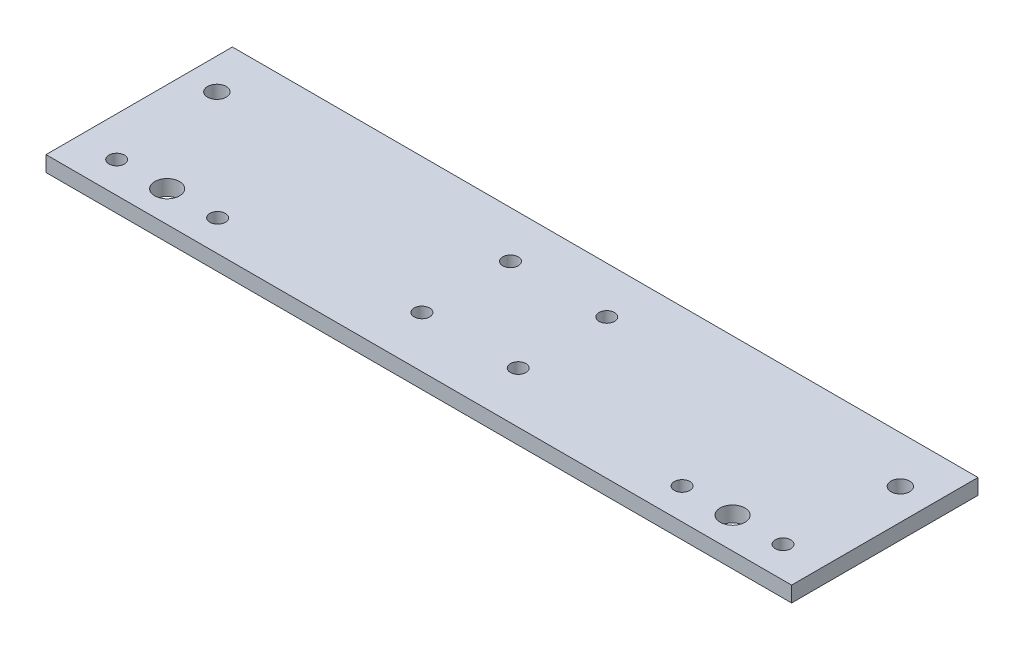
SolidWorks part; units mm, degrees
ref_plane "Front Plane" through (0, 0, 0) normal (0, 0, 1) x (1, 0, 0)
ref_plane "Top Plane" through (0, 0, 0) normal (0, 1, 0) x (1, 0, 0)
ref_plane "Right Plane" through (0, 0, 0) normal (1, 0, 0) x (0, 0, -1)
sketch "Sketch1" plane through (0, 0, 0) normal (0, 1, 0) x (1, 0, 0)
  line L0 (0, 0) -> (0, 13.3521) construction
  line L1 (-120, -45.2146) -> (120, -45.2146)
  line L2 (-120, -45.2146) -> (-120, 14.7854)
  line L3 (-120, 14.7854) -> (120, 14.7854)
  line L4 (120, -45.2146) -> (120, 14.7854)
  line L13 (0, 14.7854) -> (0, 64.2675) construction
  line L14 (-18.15, 6.4914) -> (-12.85, 6.4914) construction
  line L15 (-15.5, 6.4914) -> (-15.5, -6.9206) construction
  line L16 (-12.85, -14.4646) -> (12.85, -14.4646) construction
  line L17 (0, -14.4646) -> (0, -19.1148) construction
  circle A0 centre (-91, -35.2146) radius 4
  circle A1 centre (91, -35.2146) radius 4
  circle A2 centre (-110, -0.2146) radius 3
  circle A3 centre (110, -0.2146) radius 3
  circle A4 centre (-74.75, -35.2146) radius 2.5
  circle A5 centre (-107.25, -35.2146) radius 2.5
  circle A6 centre (107.25, -35.2146) radius 2.5
  circle A8 centre (74.75, -35.2146) radius 2.5
  circle A9 centre (-15.5, -0.2146) radius 2.5
  circle A10 centre (-15.5, -28.7146) radius 2.5
  circle A11 centre (15.5, -0.2146) radius 2.5
  circle A12 centre (15.5, -28.7146) radius 2.5
  point P0 (0, 0)
  point P48 (13.2779, -24.9637)
  dimension "D11" = 6
  dimension "D12" = 6
  dimension "D6" = 8
  dimension "D7" = 5
  dimension "D8" = 5
  dimension "D9" = 5
  dimension "D10" = 5
  dimension "D13" = 5
  dimension "D14" = 15
  dimension "D15" = 19
  dimension "D1" = 240
  dimension "D2" = 60
  dimension "D3" = 91
  dimension "D4" = 120
  dimension "D5" = 10
extrude "Boss-Extrude1" add sketch "Sketch1" along normal blind 5
